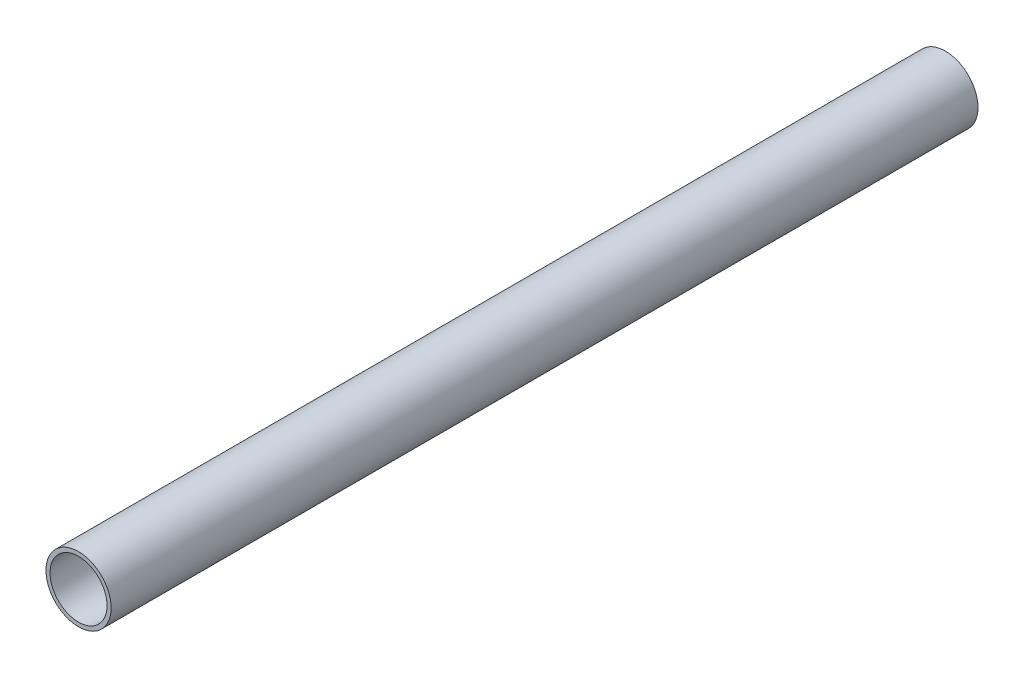
SolidWorks part; units mm, degrees
material "PC High Viscosity"
ref_plane "Front Plane" through (0, 0, 0) normal (0, 0, 1) x (1, 0, 0)
ref_plane "Top Plane" through (0, 0, 0) normal (0, 1, 0) x (1, 0, 0)
ref_plane "Right Plane" through (0, 0, 0) normal (1, 0, 0) x (0, 0, -1)
sketch "Sketch1" plane through (0, 0, 0) normal (0, 0, 1) x (1, 0, 0)
  circle A0 centre (0, 0) radius 12.7
  circle A1 centre (0, 0) radius 11.1125
  dimension "D1" = 25.4
  dimension "D2" = 1.5875
extrude "Boss-Extrude1" add sketch "Sketch1" along normal blind 337.9
